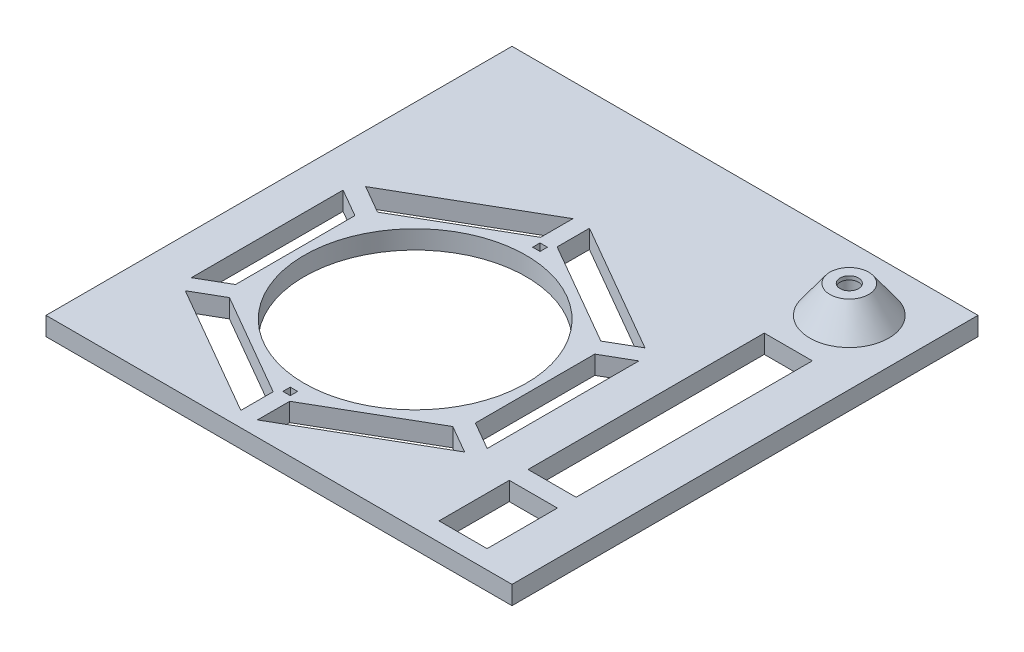
SolidWorks part; units mm, degrees
ref_plane "Front Plane" through (0, 0, 0) normal (0, 0, 1) x (1, 0, 0)
ref_plane "Top Plane" through (0, 0, 0) normal (0, 1, 0) x (1, 0, 0)
ref_plane "Right Plane" through (0, 0, 0) normal (1, 0, 0) x (0, 0, -1)
sketch "Sketch1" plane through (0, 0, 0) normal (0, 1, 0) x (1, 0, 0)
  line L1 (0, 0) -> (126, 0)
  line L2 (0, 0) -> (0, 126)
  line L3 (0, 126) -> (126, 126)
  line L4 (126, 0) -> (126, 126)
  dimension "D1" = 126
  dimension "D2" = 126
extrude "Boss-Extrude1" add sketch "Sketch1" along normal blind 5
sketch "Sketch3" plane through (0, 5, 0) normal (0, 1, 0) x (1, 0, 0)
  line L0 (108.6, 121.1) -> (108.6, 96.1) construction
  circle A0 centre (108.6, 108.6) radius 12.5
extrude "Boss-Extrude2" add sketch "Sketch3" along normal blind 7.5
sketch "Sketch4" plane through (0, 0, 0) normal (0, -1, 0) x (1, 0, 0)
  circle A1 centre (108.6, -108.6) radius 2.95
  dimension "D1" = 5.9
extrude "Cut-Extrude1" cut sketch "Sketch4" against normal blind 11.5
sketch "Sketch6" plane through (0, 12.5, 0) normal (0, 1, 0) x (1, 0, 0)
  line L0 (108.6, 121.1) -> (108.6, 96.1) construction
  circle A0 centre (108.6, 108.6) radius 12.5 construction
  circle A1 centre (108.6, 108.6) radius 2.5
  dimension "D1" = 5
extrude "Cut-Extrude2" cut sketch "Sketch6" against normal through all
chamfer "Chamfer1" distance 10 angle 36 1 edges at (108.6, 12.5, -96.1) first distance on face at (108.6, 12.5, -96.1)
sketch "Sketch8" plane through (0, 5, 0) normal (0, 1, 0) x (1, 0, 0)
  line L7 (114.2633, 24) -> (101.2633, 24)
  line L8 (114.2633, 24) -> (114.2633, 5)
  line L9 (114.2633, 5) -> (101.2633, 5)
  line L10 (101.2633, 24) -> (101.2633, 5)
  line L11 (114.2633, 24) -> (101.2633, 5) construction
  line L12 (114.2633, 5) -> (101.2633, 24) construction
  line L13 (114.2633, 24) -> (101.2633, 24)
  line L21 (114.2633, 29.0695) -> (101.2633, 29.0695)
  line L22 (114.2633, 29.0695) -> (114.2633, 92.9492)
  line L23 (114.2633, 92.9492) -> (101.2633, 92.9492)
  line L24 (101.2633, 29.0695) -> (101.2633, 92.9492)
  line L25 (114.2633, 29.0695) -> (101.2633, 92.9492) construction
  line L26 (114.2633, 92.9492) -> (101.2633, 29.0695) construction
  point P11 (107.7633, 14.5)
  point P17 (107.7633, 61.0093)
  dimension "D2" = 13
  dimension "D3" = 19
extrude "Cut-Extrude3" cut sketch "Sketch8" against normal through all contours L24 L21 L22 L23 | L7 L10 L9 L8 region at (107.7633, 5, -14.5) region at (107.7633, 5, -61.0093)
sketch "Sketch9" plane through (0, 5, 0) normal (0, 1, 0) x (1, 0, 0)
  circle A0 centre (50.8372, 48.9746) radius 30
  dimension "D1" = 60
extrude "Cut-Extrude4" cut sketch "Sketch9" against normal through all
sketch "Sketch10" plane through (0, 5, 0) normal (0, 1, 0) x (1, 0, 0)
  line L0 (50.8372, 78.9746) -> (50.8372, 18.9746) construction
  line L2 (18.3372, 67.7385) -> (18.3372, 30.2107)
  line L3 (18.3372, 30.2107) -> (50.8372, 11.4468)
  line L4 (50.8372, 11.4468) -> (83.3372, 30.2107)
  line L5 (83.3372, 30.2107) -> (83.3372, 67.7385)
  line L6 (83.3372, 67.7385) -> (50.8372, 86.5024)
  line L7 (50.8372, 86.5024) -> (18.3372, 67.7385)
  circle A0 centre (50.8372, 48.9746) radius 30 construction
  circle A1 centre (50.8372, 48.9746) radius 32.5 construction
  point P6 (0, 0)
  dimension "D1" = 65
sketch "Sketch11" plane through (0, 5, 0) normal (0, 1, 0) x (1, 0, 0)
  line L0 (50.8372, 78.9746) -> (50.8372, 86.5024) construction
  line L1 (50.8372, 11.4468) -> (50.8372, 18.9746) construction
  line L2 (51.8372, 83.7385) -> (49.8372, 83.7385)
  line L3 (51.8372, 83.7385) -> (51.8372, 81.7385)
  line L4 (51.8372, 81.7385) -> (49.8372, 81.7385)
  line L5 (49.8372, 83.7385) -> (49.8372, 81.7385)
  line L6 (51.8372, 83.7385) -> (49.8372, 81.7385) construction
  line L7 (51.8372, 81.7385) -> (49.8372, 83.7385) construction
  line L9 (51.8372, 14.2107) -> (49.8372, 14.2107)
  line L10 (51.8372, 14.2107) -> (51.8372, 16.2107)
  line L11 (51.8372, 16.2107) -> (49.8372, 16.2107)
  line L12 (49.8372, 14.2107) -> (49.8372, 16.2107)
  line L13 (51.8372, 14.2107) -> (49.8372, 16.2107) construction
  line L14 (51.8372, 16.2107) -> (49.8372, 14.2107) construction
  point P4 (50.8372, 82.7385)
  point P13 (50.8372, 15.2107)
  dimension "D1" = 2
  dimension "D2" = 2
  dimension "D3" = 2
  dimension "D4" = 2
extrude "Cut-Extrude5" cut sketch "Sketch11" against normal blind 3
sketch "Sketch13" plane through (0, 5, 0) normal (0, 1, 0) x (1, 0, 0)
  line L1 (126, 126) -> (0, 126) construction
  line L2 (50.8372, 126) -> (50.8372, 0) construction
  line L3 (0, 0) -> (126, 0) construction
  line L4 (0, 126) -> (0, 0) construction
  line L5 (0, 86.5024) -> (126, 86.5024) construction
  line L6 (126, 0) -> (126, 126) construction
  line L7 (18.3372, 126) -> (18.3372, 0) construction
  line L9 (83.3372, 126) -> (83.3372, 0) construction
sketch "Sketch14" plane through (0, 5, 0) normal (0, 1, 0) x (1, 0, 0)
  line L0 (53.0728, 93.8719) -> (88.6016, 73.3593)
  line L12 (48.6016, 85.1295) -> (20.6439, 68.9881)
  line L13 (20.6439, 68.9881) -> (13.0728, 73.3593)
  line L17 (88.6016, 73.3593) -> (81.0304, 68.9881)
  line L18 (81.0304, 68.9881) -> (53.0728, 85.1295)
  line L23 (53.0728, 85.1295) -> (53.0728, 93.8719)
  line L24 (90.8372, 69.4871) -> (90.8372, 28.462)
  line L29 (90.8372, 28.462) -> (83.266, 32.8332)
  line L30 (83.266, 32.8332) -> (83.266, 65.116)
  line L35 (83.266, 65.116) -> (90.8372, 69.4871)
  line L36 (88.6016, 24.5899) -> (53.0728, 4.0773)
  line L42 (48.6016, 93.8719) -> (48.6016, 85.1295)
  line L43 (13.0728, 73.3593) -> (48.6016, 93.8719)
  line L44 (53.0728, 4.0773) -> (53.0728, 12.8197)
  line L45 (53.0728, 12.8197) -> (81.0304, 28.961)
  line L46 (81.0304, 28.961) -> (88.6016, 24.5899)
  line L47 (48.6016, 4.0773) -> (13.0728, 24.5899)
  line L48 (13.0728, 24.5899) -> (20.6439, 28.961)
  line L49 (20.6439, 28.961) -> (48.6016, 12.8197)
  line L50 (48.6016, 12.8197) -> (48.6016, 4.0773)
  line L51 (10.8372, 28.462) -> (10.8372, 69.4871)
  line L52 (10.8372, 69.4871) -> (18.4083, 65.116)
  line L53 (18.4083, 65.116) -> (18.4083, 32.8332)
  line L54 (18.4083, 32.8332) -> (10.8372, 28.462)
  dimension "D1" = 6
extrude "Cut-Extrude6" cut sketch "Sketch14" against normal through all
